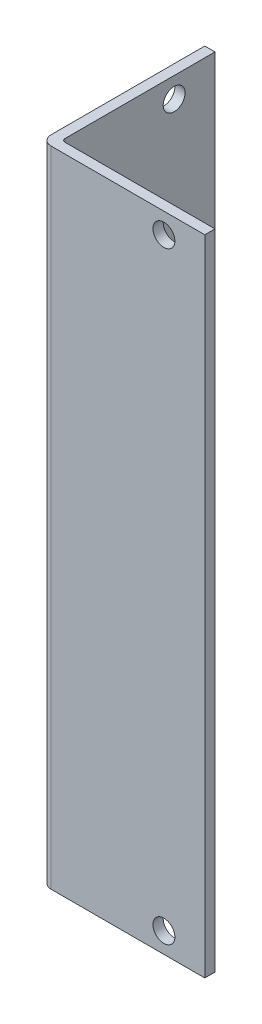
SolidWorks part; units mm, degrees
material "6061-T6 (SS)"
ref_plane "Front Plane" through (0, 0, 0) normal (0, 0, 1) x (1, 0, 0)
ref_plane "Top Plane" through (0, 0, 0) normal (0, 1, 0) x (1, 0, 0)
ref_plane "Right Plane" through (0, 0, 0) normal (1, 0, 0) x (0, 0, -1)
sketch "Sketch1" plane through (0, 0, 0) normal (0, 1, 0) x (1, 0, 0)
  line L1 (-12.7, -12.7) -> (12.7, -12.7)
  line L2 (-12.7, -12.7) -> (-12.7, 12.7)
  line L3 (-12.7, 12.7) -> (12.7, 12.7)
  line L4 (12.7, -12.7) -> (12.7, 12.7)
  line L5 (-12.7, -12.7) -> (12.7, 12.7) construction
  line L6 (-12.7, 12.7) -> (12.7, -12.7) construction
  point P0 (0, 0)
  dimension "D1" = 25.4
  dimension "D2" = 25.4
extrude "Boss-Extrude1" add sketch "Sketch1" along normal mid plane 113.5
sketch "Sketch2" plane through (0, 56.75, 0) normal (0, 1, 0) x (1, 0, 0)
  line L0 (-12.7, 12.7) -> (-12.7, -12.7) construction
  line L1 (12.7, 12.7) -> (-11.1125, 12.7)
  line L2 (12.7, 12.7) -> (12.7, -11.1125)
  line L3 (12.7, -11.1125) -> (-11.1125, -11.1125)
  line L4 (-11.1125, 12.7) -> (-11.1125, -11.1125)
  line L5 (-12.7, -12.7) -> (12.7, -12.7) construction
  dimension "D1" = 1.5875
  dimension "D2" = 1.5875
extrude "Cut-Extrude1" cut sketch "Sketch2" against normal through all
fillet "Fillet1" radius 0.508 1 edges at (-11.1125, 0, 11.1125)
hole_wizard "M3 Clearance Hole1" positions "Sketch3" profile "Sketch4" hole size "M3" standard "ANSI Metric" end condition through all
sketch "Sketch3" plane through (0, 0, 12.7) normal (0, 0, 1) x (1, 0, 0)
  line L1 (-12.7, 56.75) -> (12.7, 56.75) construction
  line L2 (12.7, 56.75) -> (12.7, -56.75) construction
  point P0 (6.35, 47.075)
  dimension "D1" = 6.35
  dimension "D2" = 9.675
sketch "Sketch4" plane through (6.35, 47.075, 12.7) normal (1, 0, 0) x (0, -1, 0)
  line L0 (0, 0) -> (0, 25.4)
  line L1 (0, 25.4) -> (1.7, 25.4)
  line L2 (1.7, 25.4) -> (1.7, 0)
  line L5 (1.7, 0) -> (0, 0)
  line L11 (0, -6.35) -> (0, 107.95) construction
  dimension "Thru Hole Dia." = 3.4
  dimension "Thru Hole Depth" = 25.4
hole_wizard "M3 Clearance Hole2" positions "Sketch5" profile "Sketch6" hole size "M3" standard "ANSI Metric" end condition through all
sketch "Sketch5" plane through (-12.7, 0, 0) normal (-1, 0, 0) x (0, 0, 1)
  line L1 (-12.7, 56.75) -> (12.7, 56.75) construction
  line L2 (-12.7, 56.75) -> (-12.7, -56.75) construction
  point P0 (-6.35, 47.075)
  dimension "D1" = 6.35
  dimension "D2" = 9.675
sketch "Sketch6" plane through (-12.7, 47.075, -6.35) normal (0, 1, 0) x (0, 0, 1)
  line L0 (0, 0) -> (0, 25.4)
  line L1 (0, 25.4) -> (1.7, 25.4)
  line L2 (1.7, 25.4) -> (1.7, 0)
  line L5 (1.7, 0) -> (0, 0)
  line L11 (0, -6.35) -> (0, 107.95) construction
  dimension "Thru Hole Dia." = 3.4
  dimension "Thru Hole Depth" = 25.4
hole_wizard "M3 Clearance Hole3" positions "Sketch7" profile "Sketch8" hole size "M3" standard "ANSI Metric" end condition through all
sketch "Sketch7" plane through (0, 0, 12.7) normal (0, 0, 1) x (1, 0, 0)
  line L2 (-12.7, -56.75) -> (12.7, -56.75) construction
  line L3 (12.7, 56.75) -> (12.7, -56.75) construction
  point P0 (6.35, -46.575)
  dimension "D1" = 6.35
  dimension "D2" = 10.175
sketch "Sketch8" plane through (6.35, -46.575, 12.7) normal (1, 0, 0) x (0, -1, 0)
  line L0 (0, 0) -> (0, 25.4)
  line L1 (0, 25.4) -> (1.7, 25.4)
  line L2 (1.7, 25.4) -> (1.7, 0)
  line L5 (1.7, 0) -> (0, 0)
  line L11 (0, -6.35) -> (0, 107.95) construction
  dimension "Thru Hole Dia." = 3.4
  dimension "Thru Hole Depth" = 25.4
hole_wizard "M3 Clearance Hole4" positions "Sketch9" profile "Sketch10" hole size "M3" standard "ANSI Metric" end condition through all
sketch "Sketch9" plane through (-12.7, 0, 0) normal (-1, 0, 0) x (0, 0, 1)
  line L1 (-12.7, -56.75) -> (12.7, -56.75) construction
  line L2 (-12.7, 56.75) -> (-12.7, -56.75) construction
  point P0 (-6.35, -46.575)
  dimension "D1" = 6.35
  dimension "D2" = 10.175
sketch "Sketch10" plane through (-12.7, -46.575, -6.35) normal (0, 1, 0) x (0, 0, 1)
  line L0 (0, 0) -> (0, 25.4)
  line L1 (0, 25.4) -> (1.7, 25.4)
  line L2 (1.7, 25.4) -> (1.7, 0)
  line L5 (1.7, 0) -> (0, 0)
  line L11 (0, -6.35) -> (0, 107.95) construction
  dimension "Thru Hole Dia." = 3.4
  dimension "Thru Hole Depth" = 25.4
fillet "Fillet2" radius 1.5 1 edges at (-12.7, 0, 12.7)
sketch "Sketch11" plane through (-12.7, 0, 0) normal (-1, 0, 0) x (0, 0, 1)
  line L0 (12.7, 56.75) -> (12.7, -56.75) construction
  line L1 (-12.7, 56.75) -> (4.2, 56.75)
  line L2 (-12.7, 56.75) -> (-12.7, 50.25)
  line L3 (-12.7, 50.25) -> (4.2, 50.25)
  line L4 (4.2, 56.75) -> (4.2, 50.25)
  line L6 (-12.7, -56.75) -> (4.2, -56.75)
  line L7 (-12.7, -56.75) -> (-12.7, -49.75)
  line L8 (-12.7, -49.75) -> (4.2, -49.75)
  line L9 (4.2, -56.75) -> (4.2, -49.75)
  dimension "D1" = 8.5
  dimension "D2" = 6.5
  dimension "D3" = 7
extrude "Cut-Extrude2" cut sketch "Sketch11" against normal up to next
sketch "Sketch12" plane through (0, 0, 12.7) normal (0, 0, 1) x (1, 0, 0)
  line L0 (-12.7, -56.75) -> (-12.7, 56.75) construction
  line L1 (12.7, 56.75) -> (-4.2, 56.75)
  line L2 (12.7, 56.75) -> (12.7, 50.25)
  line L3 (12.7, 50.25) -> (-4.2, 50.25)
  line L4 (-4.2, 56.75) -> (-4.2, 50.25)
  line L5 (12.7, -56.75) -> (-4.2, -56.75)
  line L6 (12.7, -56.75) -> (12.7, -49.75)
  line L7 (12.7, -49.75) -> (-4.2, -49.75)
  line L8 (-4.2, -56.75) -> (-4.2, -49.75)
  dimension "D1" = 8.5
  dimension "D2" = 7
  dimension "D3" = 8.5
  dimension "D4" = 6.5
extrude "Cut-Extrude3" cut sketch "Sketch12" against normal up to next
fillet "Fillet3" radius 3.81 4 edges at (-4.2, -49.75, 11.9062) (-11.9063, -49.75, 4.2) (-11.9063, 50.25, 4.2) (-4.2, 50.25, 11.9062)
sketch "Sketch13" plane through (-12.7, 0, 0) normal (-1, 0, 0) x (0, 0, 1)
  line L0 (4.2, -56.75) -> (4.2, 56.75) construction
  line L9 (2.7, -56.75) -> (2.7, 56.75) construction
  line L10 (-12.7, 50.25) -> (-12.7, -49.75) construction
  line L11 (2.7, -43.4) -> (-12.7, -43.4)
  line L12 (2.7, -43.4) -> (2.7, 43.9)
  line L13 (2.7, 43.9) -> (-12.7, 43.9)
  line L14 (-12.7, -43.4) -> (-12.7, 43.9)
  circle A2 centre (-6.35, 47.075) radius 1.7 construction
  circle A3 centre (-6.35, -46.575) radius 1.7 construction
  dimension "D2" = 3.175
  dimension "D3" = 3.175
  dimension "D1" = 1.5
extrude "Cut-Extrude4" cut sketch "Sketch13" against normal up to next
sketch "Sketch14" plane through (0, 0, 12.7) normal (0, 0, 1) x (1, 0, 0)
  line L0 (-4.2, 56.75) -> (-4.2, -56.75) construction
  line L1 (-2.7, 56.75) -> (-2.7, -56.75) construction
  line L2 (12.7, 50.25) -> (12.7, -49.75) construction
  line L3 (-2.7, -43.4) -> (12.7, -43.4)
  line L4 (-2.7, -43.4) -> (-2.7, 43.9)
  line L5 (-2.7, 43.9) -> (12.7, 43.9)
  line L6 (12.7, -43.4) -> (12.7, 43.9)
  circle A0 centre (6.35, 47.075) radius 1.7 construction
  circle A1 centre (6.35, -46.575) radius 1.7 construction
  dimension "D2" = 3.175
  dimension "D3" = 3.175
  dimension "D1" = 1.5
extrude "Cut-Extrude5" cut sketch "Sketch14" against normal up to next
chamfer "Chamfer2" distance 6.35 angle 45 4 edges at (-11.9063, 43.9, 2.7) (-2.7, 43.9, 11.9062) (-2.7, -43.4, 11.9062) (-11.9062, -43.4, 2.7)
fillet "Fillet5" radius 3.81 8 edges at (3.65, -43.4, 11.9062) (-2.7, -37.05, 11.9062) (-11.9063, -43.4, -3.65) (-11.9063, -37.05, 2.7) (-11.9063, 43.9, -3.65) (-11.9063, 37.55, 2.7) (-2.7, 37.55, 11.9062) (3.65, 43.9, 11.9062)
sketch "Sketch15" plane through (0, 56.75, 0) normal (0, 1, 0) x (1, 0, 0)
  line L0 (-11.2, -12.7) -> (-4.2, -12.7) construction
  line L1 (-12.7, -12.7) -> (-0.39, -12.7)
  line L2 (-12.7, -12.7) -> (-12.7, -0.39)
  line L3 (-12.7, -0.39) -> (-0.39, -0.39)
  line L4 (-0.39, -12.7) -> (-0.39, -0.39)
  line L5 (-12.7, -4.2) -> (-12.7, -11.2) construction
  line L6 (-0.39, -11.1125) -> (-0.39, -12.7) construction
extrude "Cut-Extrude6" cut sketch "Sketch15" against normal up to surface (6.5 mm away) up to face at (6.155, 50.25, 11.9062)
sketch "Sketch16" plane through (0, 50.25, 0) normal (0, 1, 0) x (1, 0, 0)
  line L0 (-11.2, -12.7) -> (12.7, -12.7) construction
  line L1 (-12.7, -12.7) -> (-5.7, -12.7)
  line L2 (-12.7, -12.7) -> (-12.7, -5.7)
  line L3 (-12.7, -5.7) -> (-5.7, -5.7)
  line L4 (-5.7, -12.7) -> (-5.7, -5.7)
  line L5 (-12.7, 12.7) -> (-12.7, -11.2) construction
  dimension "D1" = 7
  dimension "D2" = 7
sketch "Sketch17" plane through (0, -56.75, 0) normal (0, -1, 0) x (1, 0, 0)
  line L0 (-11.2, 12.7) -> (-4.2, 12.7) construction
  line L1 (-12.7, 12.7) -> (-0.39, 12.7)
  line L2 (-12.7, 12.7) -> (-12.7, 0.39)
  line L3 (-12.7, 0.39) -> (-0.39, 0.39)
  line L4 (-0.39, 12.7) -> (-0.39, 0.39)
  line L5 (-12.7, 4.2) -> (-12.7, 11.2) construction
  line L6 (-11.1125, 0.39) -> (-12.7, 0.39) construction
  line L7 (-0.39, 12.7) -> (-0.39, 11.1125) construction
extrude "Cut-Extrude8" cut sketch "Sketch17" against normal up to surface (7 mm away) up to face at (6.155, -49.75, 11.9062)
sketch "Sketch18" plane through (-12.7, 0, 0) normal (-1, 0, 0) x (0, 0, 1)
  line L0 (-12.7, -43.4) -> (-5.2282, -43.4) construction
  line L1 (5.7, -43.4) -> (11.2, -43.4)
  line L2 (5.7, -43.4) -> (5.7, -40.4)
  line L3 (5.7, -40.4) -> (11.2, -40.4)
  line L4 (11.2, -43.4) -> (11.2, -40.4)
  line L5 (12.7, 50.25) -> (12.7, -49.75) construction
  point P8 (8.45, -40.4)
  dimension "D1" = 5.5
  dimension "D2" = 3
  dimension "D3" = 4.25
sketch "Sketch19" plane through (0, -49.75, 0) normal (0, -1, 0) x (1, 0, 0)
  line L0 (12.7, 12.7) -> (-11.2, 12.7) construction
  line L1 (-12.7, 5.7) -> (-5.7, 5.7)
  line L2 (-12.7, 5.7) -> (-12.7, 12.7)
  line L3 (-12.7, 12.7) -> (-5.7, 12.7)
  line L4 (-5.7, 5.7) -> (-5.7, 12.7)
  line L5 (-12.7, 11.2) -> (-12.7, -12.7) construction
sketch "Sketch20" plane through (-12.7, 0, 0) normal (-1, 0, 0) x (0, 0, 1)
  line L0 (-12.7, 43.9) -> (-12.7, -43.4)
  line L14 (11.2, -49.75) -> (11.2, 50.25)
  line L15 (11.2, 50.25) -> (-12.7, 50.25)
  line L16 (-12.7, 50.25) -> (-12.7, 43.9)
  line L17 (-12.7, 43.9) -> (-5.2282, 43.9)
  line L18 (-2.5341, 42.7841) -> (1.5841, 38.6659)
  line L19 (2.7, 35.9718) -> (2.7, -35.4718)
  line L20 (1.5841, -38.1659) -> (-2.5341, -42.2841)
  line L21 (-5.2282, -43.4) -> (-12.7, -43.4)
  line L22 (-12.7, -43.4) -> (-12.7, -49.75)
  line L23 (-12.7, -49.75) -> (11.2, -49.75)
  line L27 (11.2, -49.75) -> (11.2, 50.25)
  line L28 (11.2, 50.25) -> (-12.7, 50.25)
  line L29 (-12.7, 50.25) -> (-12.7, 43.9)
  line L30 (-12.7, 43.9) -> (-5.2282, 43.9)
  line L31 (-2.5341, 42.7841) -> (1.5841, 38.6659)
  line L32 (2.7, 35.9718) -> (2.7, -35.4718)
  line L33 (1.5841, -38.1659) -> (-2.5341, -42.2841)
  line L34 (-5.2282, -43.4) -> (-12.7, -43.4)
  line L35 (-12.7, -43.4) -> (-12.7, -49.75)
  line L36 (-12.7, -49.75) -> (11.2, -49.75)
  arc A6 (-2.5341, 42.7841) -> (-5.2282, 43.9) centre (-5.2282, 40.09) ccw
  arc A7 (2.7, 35.9718) -> (1.5841, 38.6659) centre (-1.11, 35.9718) ccw
  arc A8 (1.5841, -38.1659) -> (2.7, -35.4718) centre (-1.11, -35.4718) ccw
  arc A9 (-5.2282, -43.4) -> (-2.5341, -42.2841) centre (-5.2282, -39.59) ccw
  arc A11 (-2.5341, 42.7841) -> (-5.2282, 43.9) centre (-5.2282, 40.09) ccw
  arc A12 (2.7, 35.9718) -> (1.5841, 38.6659) centre (-1.11, 35.9718) ccw
  arc A13 (1.5841, -38.1659) -> (2.7, -35.4718) centre (-1.11, -35.4718) ccw
  arc A14 (-5.2282, -43.4) -> (-2.5341, -42.2841) centre (-5.2282, -39.59) ccw
  line M26 (-12.7, 43.9) -> (-5.2282, 43.9)
  arc M27 (-5.2282, 43.9) -> (-2.5341, 42.7841) centre (-5.2282, 40.09) cw
  line M28 (-2.5341, 42.7841) -> (1.5841, 38.6659)
  arc M29 (1.5841, 38.6659) -> (2.7, 35.9718) centre (-1.11, 35.9718) cw
  line M30 (2.7, 35.9718) -> (2.7, -35.4718)
  arc M31 (2.7, -35.4718) -> (1.5841, -38.1659) centre (-1.11, -35.4718) cw
  line M32 (1.5841, -38.1659) -> (-2.5341, -42.2841)
  arc M33 (-2.5341, -42.2841) -> (-5.2282, -43.4) centre (-5.2282, -39.59) cw
  line M34 (-5.2282, -43.4) -> (-12.7, -43.4)
  dimension "D1" = 0
extrude "Boss-Extrude2" add sketch "Sketch20" against normal up to surface (1.5875 mm away) contours L0 M26 M34 M33 M32 M31 M30 M29 M28 M27 region at (-12.7, 0.25, -5.177) up to face at (-11.1125, -46.575, -4.65)
sketch "Sketch21" plane through (0, 0, 12.7) normal (0, 0, 1) x (1, 0, 0)
  line L0 (12.7, 43.9) -> (12.7, -43.4)
  line L14 (-11.2, 50.25) -> (-11.2, -49.75)
  line L15 (-11.2, -49.75) -> (12.7, -49.75)
  line L16 (12.7, -49.75) -> (12.7, -43.4)
  line L17 (12.7, -43.4) -> (5.2282, -43.4)
  line L18 (2.5341, -42.2841) -> (-1.5841, -38.1659)
  line L19 (-2.7, -35.4718) -> (-2.7, 35.9718)
  line L20 (-1.5841, 38.6659) -> (2.5341, 42.7841)
  line L21 (5.2282, 43.9) -> (12.7, 43.9)
  line L22 (12.7, 43.9) -> (12.7, 50.25)
  line L23 (12.7, 50.25) -> (-11.2, 50.25)
  line L27 (-11.2, 50.25) -> (-11.2, -49.75)
  line L28 (-11.2, -49.75) -> (12.7, -49.75)
  line L29 (12.7, -49.75) -> (12.7, -43.4)
  line L30 (12.7, -43.4) -> (5.2282, -43.4)
  line L31 (2.5341, -42.2841) -> (-1.5841, -38.1659)
  line L32 (-2.7, -35.4718) -> (-2.7, 35.9718)
  line L33 (-1.5841, 38.6659) -> (2.5341, 42.7841)
  line L34 (5.2282, 43.9) -> (12.7, 43.9)
  line L35 (12.7, 43.9) -> (12.7, 50.25)
  line L36 (12.7, 50.25) -> (-11.2, 50.25)
  arc A6 (2.5341, -42.2841) -> (5.2282, -43.4) centre (5.2282, -39.59) ccw
  arc A7 (-2.7, -35.4718) -> (-1.5841, -38.1659) centre (1.11, -35.4718) ccw
  arc A8 (-1.5841, 38.6659) -> (-2.7, 35.9718) centre (1.11, 35.9718) ccw
  arc A9 (5.2282, 43.9) -> (2.5341, 42.7841) centre (5.2282, 40.09) ccw
  arc A11 (2.5341, -42.2841) -> (5.2282, -43.4) centre (5.2282, -39.59) ccw
  arc A12 (-2.7, -35.4718) -> (-1.5841, -38.1659) centre (1.11, -35.4718) ccw
  arc A13 (-1.5841, 38.6659) -> (-2.7, 35.9718) centre (1.11, 35.9718) ccw
  arc A14 (5.2282, 43.9) -> (2.5341, 42.7841) centre (5.2282, 40.09) ccw
  line M24 (12.7, -43.4) -> (5.2282, -43.4)
  arc M25 (5.2282, -43.4) -> (2.5341, -42.2841) centre (5.2282, -39.59) cw
  line M26 (2.5341, -42.2841) -> (-1.5841, -38.1659)
  arc M27 (-1.5841, -38.1659) -> (-2.7, -35.4718) centre (1.11, -35.4718) cw
  line M28 (-2.7, -35.4718) -> (-2.7, 35.9718)
  arc M29 (-2.7, 35.9718) -> (-1.5841, 38.6659) centre (1.11, 35.9718) cw
  line M30 (-1.5841, 38.6659) -> (2.5341, 42.7841)
  arc M31 (2.5341, 42.7841) -> (5.2282, 43.9) centre (5.2282, 40.09) cw
  line M32 (5.2282, 43.9) -> (12.7, 43.9)
  dimension "D1" = 0
extrude "Boss-Extrude3" add sketch "Sketch21" against normal up to surface (1.5875 mm away) contours L0 M32 M31 M30 M29 M28 M27 M26 M25 M24 region at (5.177, 0.25, 12.7) up to face at (8.05, -46.575, 11.1125)
